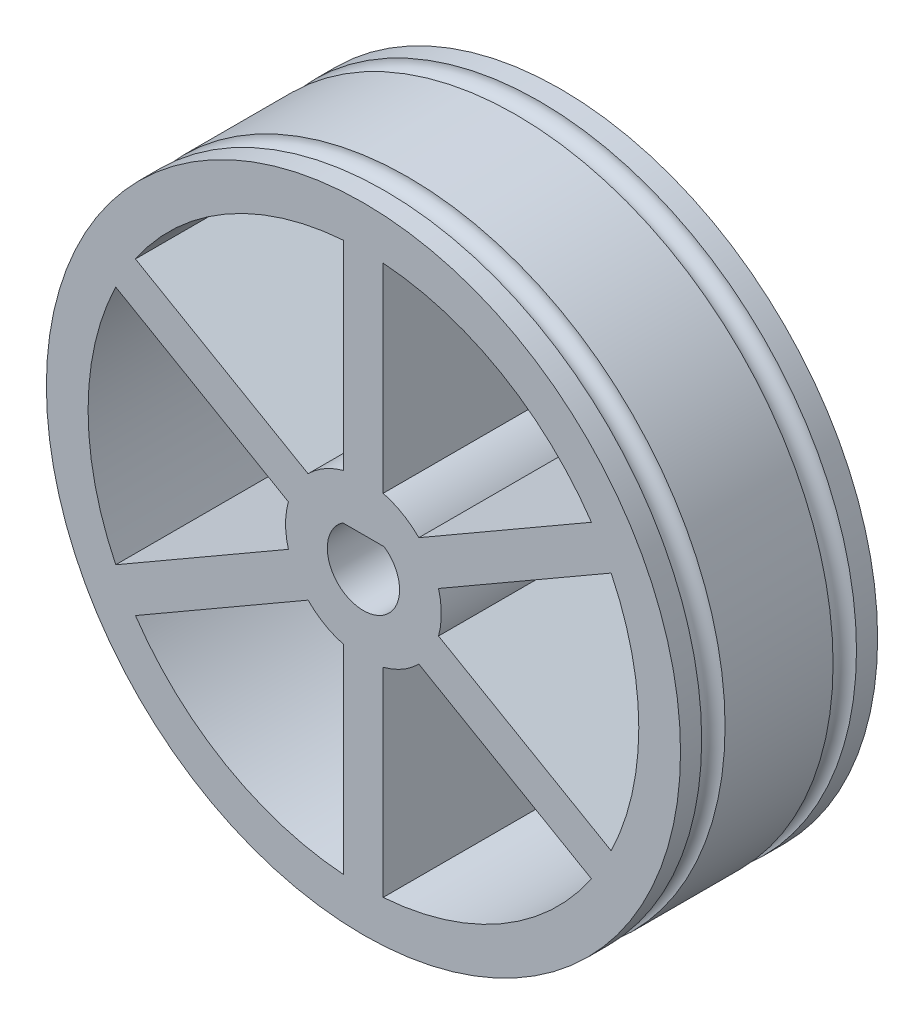
SolidWorks part; units mm, degrees
ref_plane "Front Plane" through (0, 0, 0) normal (0, 0, 1) x (1, 0, 0)
ref_plane "Top Plane" through (0, 0, 0) normal (0, 1, 0) x (1, 0, 0)
ref_plane "Right Plane" through (0, 0, 0) normal (1, 0, 0) x (0, 0, -1)
sketch "Sketch1" plane through (0, 0, 0) normal (0, 0, 1) x (1, 0, 0)
  circle A0 centre (0, 0) radius 24.13
  circle A1 centre (0, 0) radius 20.955
  circle A2 centre (0, 0) radius 2.75
  circle A3 centre (0, 0) radius 5.925
  dimension "D1" = 48.26
  dimension "D2" = 3.175
  dimension "D3" = 5.5
  dimension "D4" = 3.175
extrude "Boss-Extrude1" add sketch "Sketch1" along normal blind 15 contours A0 A1 | A3 A2 region at (-23.4475, 0, 0) region at (-5.7574, 0, 0)
sketch "Sketch3" plane through (0, 0, 0) normal (0, 0, -1) x (-1, 0, 0)
  line L0 (0, 0) -> (0, 2.75) construction
  line L1 (1.5, 2.75) -> (-1.5, 2.75)
  line L2 (0, 2.75) -> (0, 20.955) construction
  line L3 (1.5, 20.955) -> (-1.5, 20.955)
  line L4 (-1.5, 20.955) -> (-1.5, 2.75)
  line L5 (1.5, 20.955) -> (1.5, 2.75)
  circle A0 centre (0, 0) radius 2.75 construction
  circle A1 centre (0, 0) radius 20.955 construction
  point P7 (0, 2.75)
  point P14 (0, 20.955)
  dimension "D1" = 3
  dimension "D2" = 3
extrude "Boss-Extrude3" add sketch "Sketch3" against normal up to surface (15 mm away) up to face at (2.75, 0, 15)
pattern_circular "CirPattern1" count 6 over 360 about axis through (0, 0, 15) along (0, 0, 1) of "Boss-Extrude3"
sketch "Sketch4" plane through (0, 0, 0) normal (1, 0, 0) x (0, 0, -1)
  line L0 (0, 0) -> (0, 24.13) construction
  line L1 (0, 24.13) -> (-15, 24.13) construction
  line L2 (-2.5, 24.13) -> (-12.5, 24.13) construction
  line L3 (0, 0) -> (-22.4846, 0) construction
  circle A0 centre (-12.5, 24.13) radius 0.89
  circle A1 centre (-2.5, 24.13) radius 0.89
  point P9 (-7.5, 24.13)
  dimension "D3" = 1.78
  dimension "D1" = 15
  dimension "D2" = 10
  dimension "D4" = 24.13
  dimension "D5" = 2.5
revolve "Cut-Revolve1" cut sketch "Sketch4" angle 360 about L3
sketch "Sketch5" plane through (0, 0, 15) normal (0, 0, 1) x (1, 0, 0)
  line L0 (0, 0) -> (0, 2.75) construction
  line L1 (-2.5, 2.75) -> (2.5, 2.75)
  line L2 (-2.5, 2.75) -> (-2.5, 2.25)
  line L3 (2.5, 2.75) -> (2.5, 2.25)
  line L4 (2.5, 2.25) -> (-2.5, 2.25)
  circle A0 centre (0, 0) radius 2.75 construction
  point P9 (0, 2.75)
  dimension "D1" = 5
  dimension "D2" = 0.5
extrude "Boss-Extrude4" add sketch "Sketch5" against normal up to surface (15 mm away) up to face at (6.4306, 11.1382, 0)
ref_plane "Plane2" through (0, 0, 12.5) normal (0, 0, 1) x (1, 0, 0)
ref_plane "Plane3" through (0, 0, 2.5) normal (0, 0, -1) x (-1, 0, 0)
